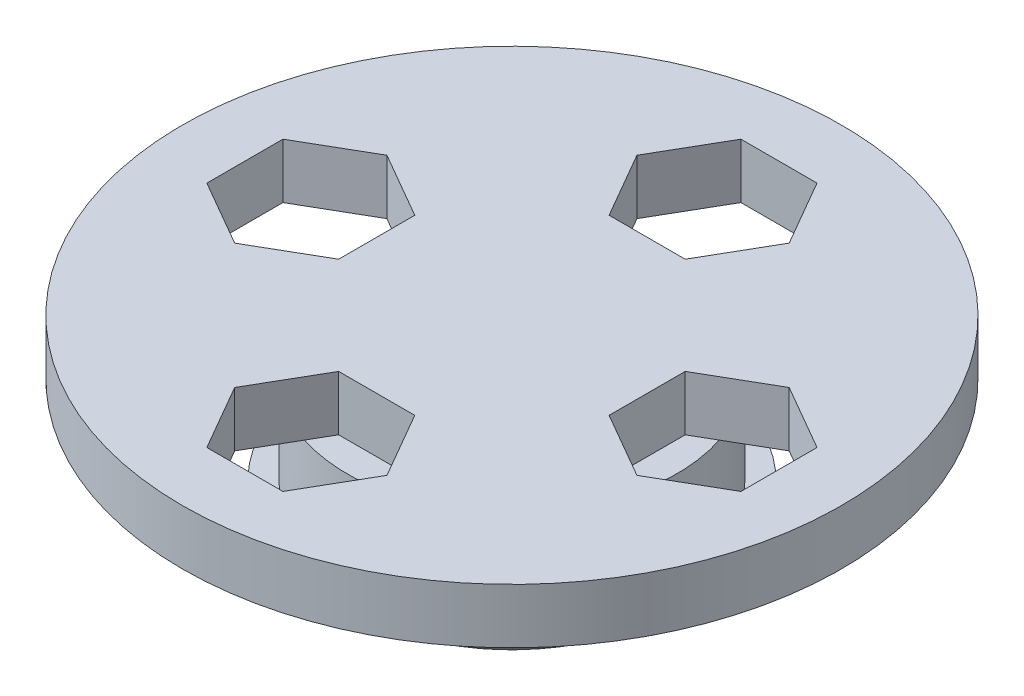
SolidWorks part; units mm, degrees
ref_plane "Alzado" through (0, 0, 0) normal (0, 0, 1) x (1, 0, 0)
ref_plane "Planta" through (0, 0, 0) normal (0, 1, 0) x (1, 0, 0)
ref_plane "Vista lateral" through (0, 0, 0) normal (1, 0, 0) x (0, 0, -1)
sketch "Croquis1" plane through (0, 0, 0) normal (0, 1, 0) x (1, 0, 0)
  circle A0 centre (0, 0) radius 8.5
  dimension "D1" = 17
extrude "Saliente-Extruir1" add sketch "Croquis1" along normal blind 2
sketch "Croquis2" plane through (0, 2, 0) normal (0, 1, 0) x (1, 0, 0)
  circle A0 centre (0, 0) radius 7.5
  dimension "D1" = 15
extrude "Saliente-Extruir2" add sketch "Croquis2" along normal blind 4
sketch "Croquis3" plane through (0, 6, 0) normal (0, 1, 0) x (1, 0, 0)
  circle A0 centre (0, 0) radius 15
  dimension "D1" = 30
extrude "Saliente-Extruir3" add sketch "Croquis3" along normal blind 2.5
fillet "Redondeo1" radius 3 1 edges at (0, 0, 8.5)
sketch "Croquis4" plane through (0, 8.5, 0) normal (0, 1, 0) x (1, 0, 0)
  line L0 (12.154, -1.7321) -> (12.154, 1.7321)
  line L1 (3.4641, 9.154) -> (1.7321, 12.154)
  line L2 (1.7321, 12.154) -> (-1.7321, 12.154)
  line L3 (-1.7321, 12.154) -> (-3.4641, 9.154)
  line L4 (-3.4641, 9.154) -> (-1.7321, 6.154)
  line L5 (-1.7321, 6.154) -> (1.7321, 6.154)
  line L6 (1.7321, 6.154) -> (3.4641, 9.154)
  line L7 (12.154, 1.7321) -> (9.154, 3.4641)
  line L8 (9.154, 3.4641) -> (6.154, 1.7321)
  line L9 (6.154, 1.7321) -> (6.154, -1.7321)
  line L10 (6.154, -1.7321) -> (9.154, -3.4641)
  line L11 (9.154, -3.4641) -> (12.154, -1.7321)
  line L12 (-1.7321, -12.154) -> (1.7321, -12.154)
  line L13 (1.7321, -12.154) -> (3.4641, -9.154)
  line L14 (3.4641, -9.154) -> (1.7321, -6.154)
  line L15 (1.7321, -6.154) -> (-1.7321, -6.154)
  line L16 (-1.7321, -6.154) -> (-3.4641, -9.154)
  line L17 (-3.4641, -9.154) -> (-1.7321, -12.154)
  line L18 (-12.154, 1.7321) -> (-12.154, -1.7321)
  line L19 (-12.154, -1.7321) -> (-9.154, -3.4641)
  line L20 (-9.154, -3.4641) -> (-6.154, -1.7321)
  line L21 (-6.154, -1.7321) -> (-6.154, 1.7321)
  line L22 (-6.154, 1.7321) -> (-9.154, 3.4641)
  line L23 (-9.154, 3.4641) -> (-12.154, 1.7321)
  circle A0 centre (0, 9.154) radius 3 construction
  point P29 (0, 0)
  dimension "D1" = 6
  dimension "D2" = 4
extrude "Cortar-Extruir1" cut sketch "Croquis4" against normal blind 2.5
